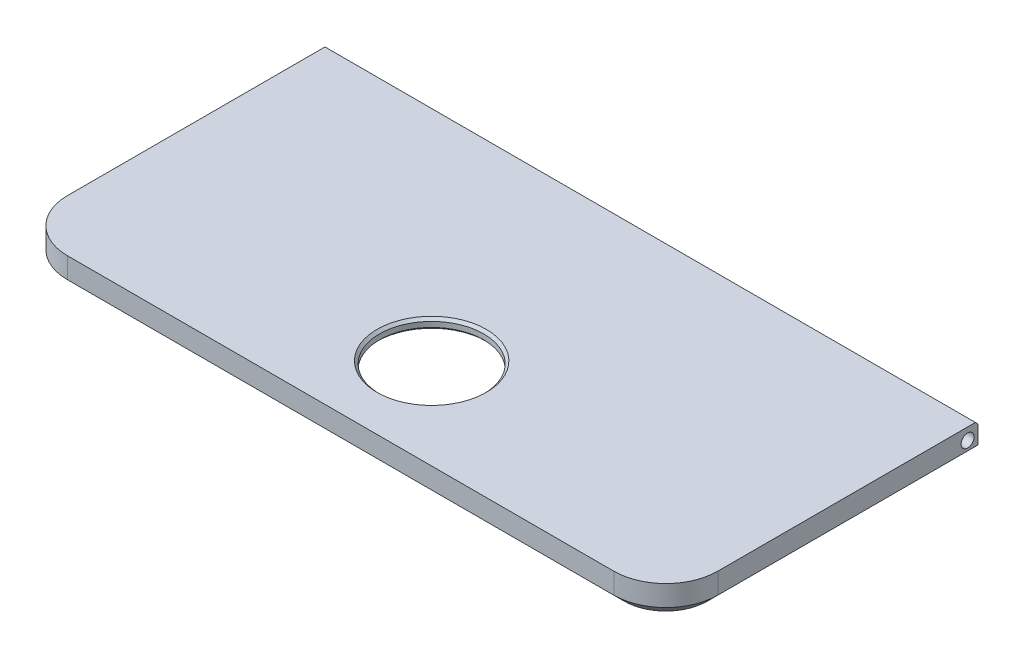
SolidWorks part; units mm, degrees
material "ПК/АБС"
ref_plane "Спереди" through (0, 0, 0) normal (0, 0, 1) x (1, 0, 0)
ref_plane "Сверху" through (0, 0, 0) normal (0, 1, 0) x (1, 0, 0)
ref_plane "Справа" through (0, 0, 0) normal (1, 0, 0) x (0, 0, -1)
sketch "Эскиз1" plane through (0, 0, 0) normal (0, 1, 0) x (1, 0, 0)
  line L1 (-62.5, -30) -> (62.5, -30)
  line L2 (-62.5, -30) -> (-62.5, 30)
  line L3 (-62.5, 30) -> (62.5, 30)
  line L4 (62.5, -30) -> (62.5, 30)
  line L5 (-62.5, -30) -> (62.5, 30) construction
  line L6 (-62.5, 30) -> (62.5, -30) construction
  point P0 (0, 0)
  dimension "D1" = 125
  dimension "D2" = 60
extrude "Бобышка-Вытянуть1" add sketch "Эскиз1" along normal blind 6
fillet "Скругление1" radius 10 2 edges at (-62.5, 3, 30) (62.5, 3, 30)
sketch "Эскиз2" plane through (0, 0, 0) normal (0, -1, 0) x (1, 0, 0)
  line L8 (-59, 20) -> (-59, -26.5)
  line L9 (-59, -26.5) -> (59, -26.5)
  line L10 (59, -26.5) -> (59, 20)
  line L11 (52.5, 26.5) -> (-52.5, 26.5)
  line L12 (-59, 20) -> (-59, -26.5)
  line L13 (-59, -26.5) -> (59, -26.5)
  line L14 (59, -26.5) -> (59, 20)
  line L15 (52.5, 26.5) -> (-52.5, 26.5)
  arc A4 (59, 20) -> (52.5, 26.5) centre (52.5, 20) ccw
  arc A5 (-52.5, 26.5) -> (-59, 20) centre (-52.5, 20) ccw
  arc A6 (59, 20) -> (52.5, 26.5) centre (52.5, 20) ccw
  arc A7 (-52.5, 26.5) -> (-59, 20) centre (-52.5, 20) ccw
  dimension "D1" = 3.5
extrude "Вырез-Вытянуть1" cut sketch "Эскиз2" against normal blind 4
chamfer "Фаска1" distance 2 angle 45 6 edges at (0, 0, -30) (-62.5, 0, -5) (62.5, 0, -5) (-59.5711, 0, 27.0711) (59.5711, 0, 27.0711) (0, 0, 30)
sketch "Эскиз4" plane through (0, 4, 0) normal (0, -1, 0) x (1, 0, 0)
  line L6 (-59, -26.5) -> (59, -26.5)
  line L7 (-59, -26.5) -> (-59, -25)
  line L8 (-59, -25) -> (59, -25)
  line L9 (59, -26.5) -> (59, -25)
  line L14 (62.5, -30) -> (-62.5, -30) construction
  dimension "D2" = 5
extrude "Бобышка-Вытянуть3" add sketch "Эскиз4" along normal up to surface (4 mm away) up to face at (0, 0, 7.219)
sketch "Эскиз3" plane through (62.5, 0, 0) normal (1, 0, 0) x (0, 0, -1)
  line L0 (-20, 6) -> (30, 6) construction
  line L1 (30, 6) -> (30, 2) construction
  circle A0 centre (28, 3.75) radius 1.25
  dimension "D2" = 2.5
  dimension "D1" = 2.25
  dimension "D3" = 2
extrude "Вырез-Вытянуть2" cut sketch "Эскиз3" against normal blind 10
sketch "Эскиз5" plane through (-62.5, 0, 0) normal (-1, 0, 0) x (0, 0, 1)
  line L0 (-30, 6) -> (-30, 2) construction
  line L1 (-30, 6) -> (20, 6) construction
  circle A0 centre (-28, 3.75) radius 1.25
  dimension "D3" = 2.5
  dimension "D1" = 2
  dimension "D2" = 2.25
extrude "Вырез-Вытянуть3" cut sketch "Эскиз5" against normal blind 10
sketch "Эскиз6" plane through (0, 4, 0) normal (0, -1, 0) x (1, 0, 0)
  line L0 (0, 30) -> (0, 12.5) construction
  line L1 (-52.5, 30) -> (52.5, 30) construction
  circle A0 centre (0, 12.5) radius 10
  dimension "D2" = 20
  dimension "D1" = 17.5
extrude "Вырез-Вытянуть4" cut sketch "Эскиз6" against normal up to surface (2 mm away) up to face at (0, 6, 7.357)
chamfer "Фаска2" distance 0.5 angle 45 3 edges at (0, 6, -30) (0, 4, 2.5) (0, 6, 2.5)
